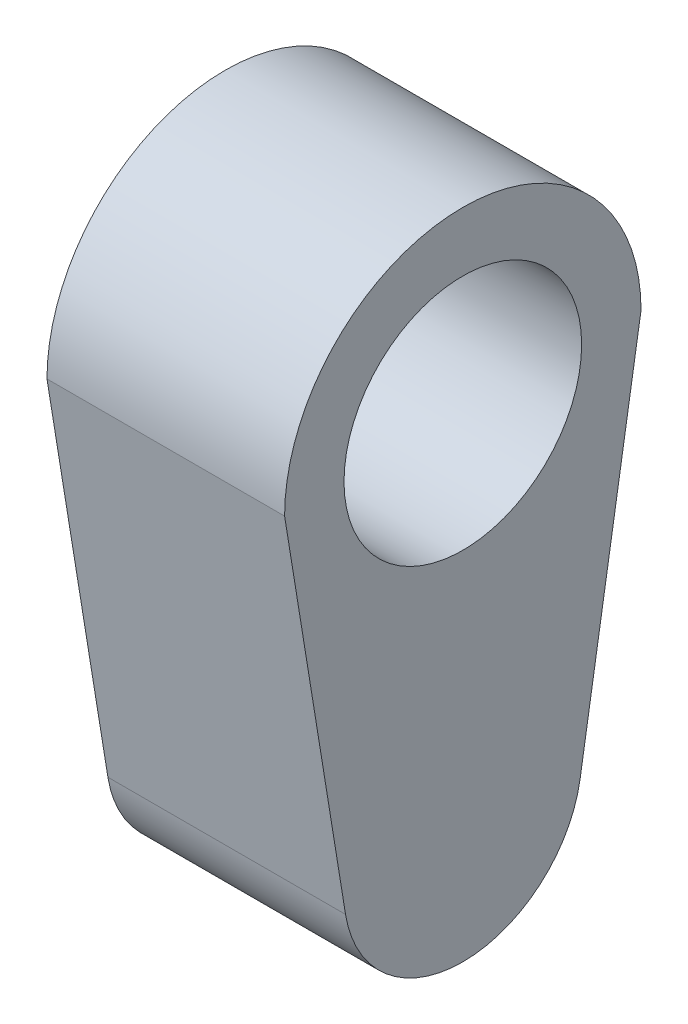
SolidWorks part; units mm, degrees
ref_plane "Front Plane" through (0, 0, 0) normal (0, 0, 1) x (1, 0, 0)
ref_plane "Top Plane" through (0, 0, 0) normal (0, 1, 0) x (1, 0, 0)
ref_plane "Right Plane" through (0, 0, 0) normal (1, 0, 0) x (0, 0, -1)
sketch "Sketch1" plane through (0, 0, 0) normal (1, 0, 0) x (0, 0, -1)
  line L0 (-3.81, 0) -> (-2.5072, -8.0269)
  line L1 (3.81, 0) -> (2.5072, -8.0269)
  circle A0 centre (0, 0) radius 2.54
  arc A1 (3.81, 0) -> (-3.81, 0) centre (0, 0) ccw
  arc A2 (-2.5072, -8.0269) -> (2.5072, -8.0269) centre (0, -7.62) ccw
  point P6 (-0.8911, -5.926)
  point P9 (-0.0724, -6.646)
  point P10 (0, 0)
  point P12 (-2.2773, 0)
  point P13 (0, -5.7037)
  point P14 (1.2357, -5.5006)
  point P15 (1.1649, -5.3779)
  dimension "D1" = 5.08
  dimension "D2" = 7.62
  dimension "D4" = 2.54
  dimension "D3" = 7.62
extrude "Boss-Extrude1" add sketch "Sketch1" along normal blind 5.08
extrude "Boss-Extrude2" add sketch "Sketch1<2>" along normal blind 1.016 contours A0 region at (0, 0, 0)
sketch "Sketch1<2>" plane through (0, 0, 0) normal (1, 0, 0) x (0, 0, -1) same geometry as "Sketch1"
